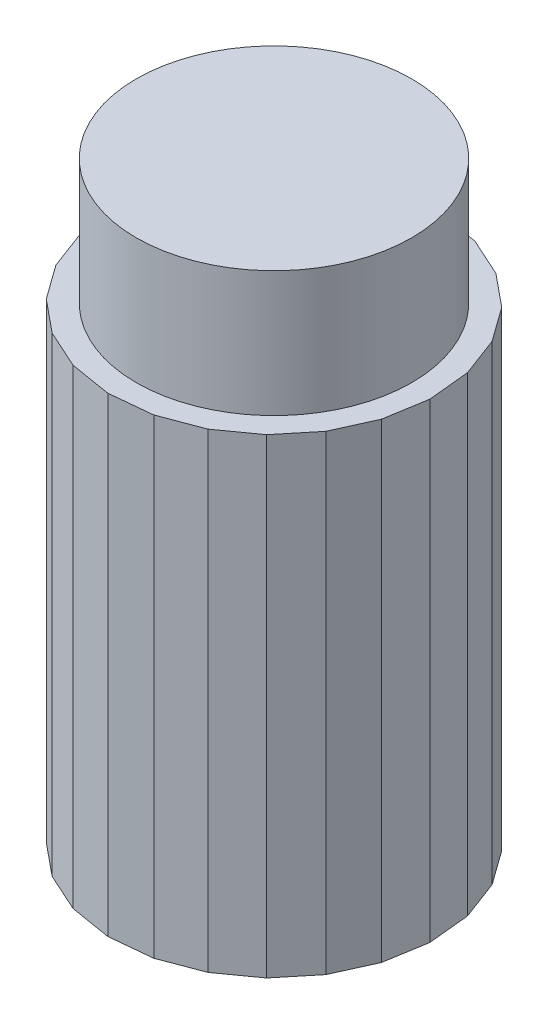
SolidWorks part; units mm, degrees
ref_plane "Спереди" through (0, 0, 0) normal (0, 0, 1) x (1, 0, 0)
ref_plane "Сверху" through (0, 0, 0) normal (0, 1, 0) x (1, 0, 0)
ref_plane "Справа" through (0, 0, 0) normal (1, 0, 0) x (0, 0, -1)
sketch "Эскиз1" plane through (0, 0, 0) normal (0, 1, 0) x (1, 0, 0)
  line L25 (1.6524, 51.335) -> (-11.6904, 50.0134)
  line L26 (-11.6904, 50.0134) -> (-24.2365, 45.2836)
  line L27 (-24.2365, 45.2836) -> (-35.1309, 37.4677)
  line L28 (-35.1309, 37.4677) -> (-43.6312, 27.0985)
  line L29 (-43.6312, 27.0985) -> (-49.1581, 14.8825)
  line L30 (-49.1581, 14.8825) -> (-51.335, 1.6524)
  line L31 (-51.335, 1.6524) -> (-50.0134, -11.6904)
  line L32 (-50.0134, -11.6904) -> (-45.2836, -24.2365)
  line L33 (-45.2836, -24.2365) -> (-37.4677, -35.1309)
  line L34 (-37.4677, -35.1309) -> (-27.0985, -43.6312)
  line L35 (-27.0985, -43.6312) -> (-14.8825, -49.1581)
  line L36 (-14.8825, -49.1581) -> (-1.6524, -51.335)
  line L37 (-1.6524, -51.335) -> (11.6904, -50.0134)
  line L38 (11.6904, -50.0134) -> (24.2365, -45.2836)
  line L39 (24.2365, -45.2836) -> (35.1309, -37.4677)
  line L40 (35.1309, -37.4677) -> (43.6312, -27.0985)
  line L41 (43.6312, -27.0985) -> (49.1581, -14.8825)
  line L42 (49.1581, -14.8825) -> (51.335, -1.6524)
  line L43 (51.335, -1.6524) -> (50.0134, 11.6904)
  line L44 (50.0134, 11.6904) -> (45.2836, 24.2365)
  line L45 (45.2836, 24.2365) -> (37.4677, 35.1309)
  line L46 (37.4677, 35.1309) -> (27.0985, 43.6312)
  line L47 (27.0985, 43.6312) -> (14.8825, 49.1581)
  line L48 (14.8825, 49.1581) -> (1.6524, 51.335)
  circle A1 centre (0, 0) radius 50.9221 construction
extrude "Бобышка-Вытянуть1" add sketch "Эскиз1" along normal blind 150
sketch "Эскиз2" plane through (0, 150, 0) normal (0, 1, 0) x (1, 0, 0)
  circle A0 centre (0, 0) radius 43.8999
extrude "Бобышка-Вытянуть2" add sketch "Эскиз2" along normal blind 40
